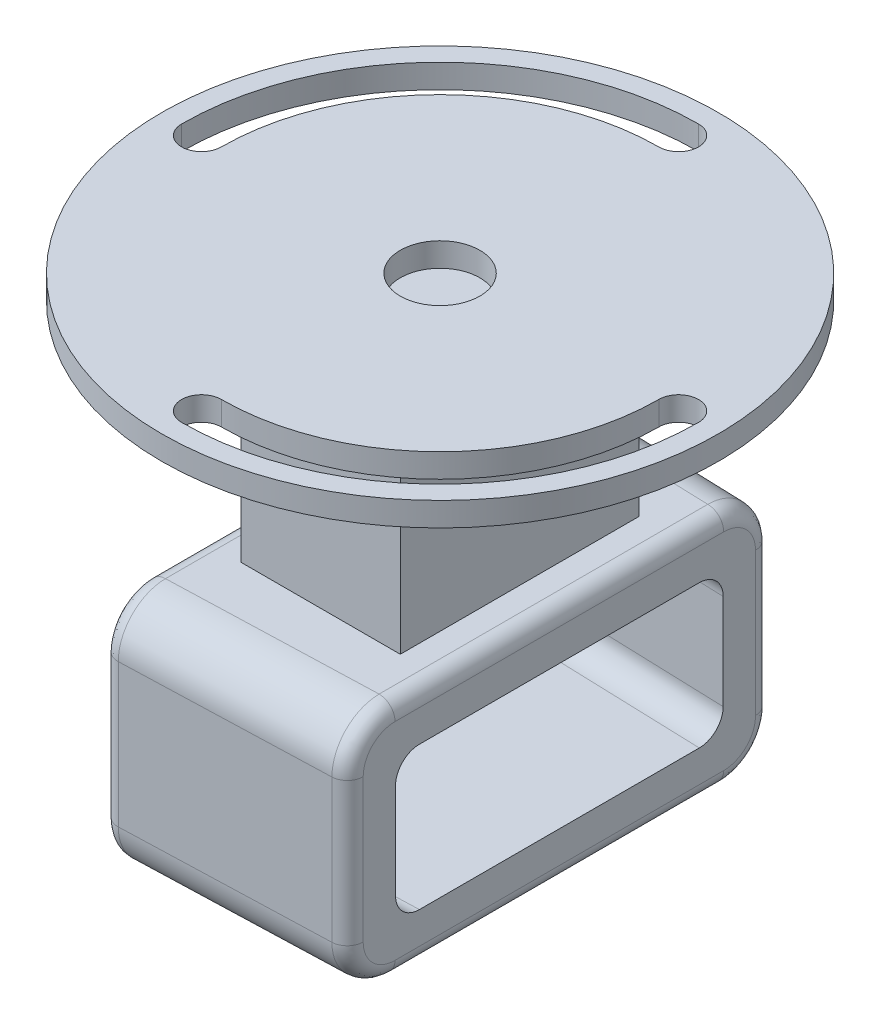
SolidWorks part; units mm, degrees
ref_plane "정면" through (0, 0, 0) normal (0, 0, 1) x (1, 0, 0)
ref_plane "윗면" through (0, 0, 0) normal (0, 1, 0) x (1, 0, 0)
ref_plane "우측면" through (0, 0, 0) normal (1, 0, 0) x (0, 0, -1)
sketch "스케치1" plane through (0, 0, 0) normal (0, 1, 0) x (1, 0, 0)
  circle A0 centre (0, 0) radius 35
  circle A1 centre (0, 0) radius 32.5 construction
  circle A2 centre (0, 0) radius 27.5 construction
  circle A3 centre (0, 0) radius 30 construction
  arc A4 (0, 27.5) -> (0, 32.5) centre (0, 30) ccw
  arc A5 (32.5, 0) -> (27.5, 0) centre (30, 0) ccw
  arc A6 (0, -27.5) -> (0, -32.5) centre (0, -30) ccw
  arc A7 (-32.5, 0) -> (-27.5, 0) centre (-30, 0) ccw
  arc A8 (-27.5, 0) -> (0, 27.5) centre (0, 0) cw
  arc A9 (-32.5, 0) -> (0, 32.5) centre (0, 0) cw
  arc A10 (0, -27.5) -> (27.5, 0) centre (0, 0) ccw
  arc A11 (0, -32.5) -> (32.5, 0) centre (0, 0) ccw
  circle A12 centre (0, 0) radius 5
  dimension "D1" = 70
  dimension "D2" = 65
  dimension "D3" = 60
  dimension "D4" = 55
  dimension "D5" = 10
extrude "보스-돌출1" add sketch "스케치1" along normal blind 3
sketch "스케치2" plane through (0, 0, 0) normal (0, -1, 0) x (1, 0, 0)
  line L1 (-10, -15) -> (10, -15)
  line L2 (-10, -15) -> (-10, 15)
  line L3 (-10, 15) -> (10, 15)
  line L4 (10, -15) -> (10, 15)
  line L5 (-10, -15) -> (10, 15) construction
  line L6 (-10, 15) -> (10, -15) construction
  point P0 (0, 0)
  dimension "D1" = 20
  dimension "D2" = 30
extrude "보스-돌출2" add sketch "스케치2" along normal blind 26
sketch "스케치5" plane through (0, -26, 0) normal (0, -1, 0) x (1, 0, 0)
  line L0 (15, 20.6) -> (15, -20.6)
  line L2 (15, -20.6) -> (-15, -21.6)
  line L3 (-15, -21.6) -> (-15, 21.6)
  line L4 (-15, 21.6) -> (15, 20.6)
  line L5 (15, 0) -> (-15, 0) construction
  line L6 (10, 15) -> (-10, 15) construction
  line L7 (10, -15) -> (10, 15) construction
  line L9 (-10, 15) -> (-10, -15) construction
  point P18 (0, 0)
  dimension "D1" = 41.2
  dimension "D2" = 43.2
  dimension "D3" = 15
  dimension "D4" = 30
  dimension "D5" = 10
extrude "보스-돌출4" add sketch "스케치5" along normal blind 6
sketch "스케치6" plane through (0, -26, 0) normal (0, 1, 0) x (1, 0, 0)
  line L0 (-15, -21.6) -> (-15, -27.6)
  line L1 (-15, -27.6) -> (15, -26.6)
  line L2 (15, -26.6) -> (15, -20.6)
  line L3 (15, -20.6) -> (-15, -21.6)
  line L4 (-15, 21.6) -> (-15, 27.6)
  line L5 (-15, 27.6) -> (15, 26.6)
  line L6 (15, 26.6) -> (15, 20.6)
  line L7 (15, 20.6) -> (-15, 21.6)
  line L8 (-15, 21.6) -> (15, 20.6) construction
  line L9 (15, 20.6) -> (15, -20.6) construction
  dimension "D1" = 6
  dimension "D2" = 6
  dimension "D3" = 6
  dimension "D4" = 6
extrude "보스-돌출5" add sketch "스케치6" against normal blind 30
extrude "보스-돌출6" add sketch "스케치5<2>" against normal blind 6 from surface starting at face at (0, -56, 24.1)
sketch "스케치5<2>" plane through (0, -26, 0) normal (0, -1, 0) x (1, 0, 0) same geometry as "스케치5"
fillet "필렛1" radius 3 4 edges at (0, -32, -21.1) (0, -50, -21.1) (0, -50, 21.1) (0, -32, 21.1)
fillet "필렛2" radius 6 4 edges at (0, -26, 27.1) (0, -26, -27.1) (0, -56, -27.1) (0, -56, 27.1)
fillet "필렛3" radius 2 16 edges at (15, -54.2426, 24.8417) (15, -41, 26.6) (15, -27.7574, 24.8417) (15, -26, 0) (15, -27.7574, -24.8417) (15, -41, -26.6) (15, -54.2426, -24.8417) (-15, -54.2426, -25.8417) (-15, -41, -27.6) (-15, -27.7574, -25.8417) (-15, -26, 0) (-15, -27.7574, 25.8417) (-15, -41, 27.6) (-15, -54.2426, 25.8417) (15, -56, 0) (-15, -56, 0)
ref_plane "평면1" through (0, -56, 0) normal (0, -1, 0) x (-1, 0, 0)
sketch "스케치7" plane through (0, -56, 0) normal (0, -1, 0) x (-1, 0, 0)
  line L0 (0, 0) -> (15, 0) construction
  line L2 (15, 21.6) -> (15, -21.6) construction
  line L3 (15, 9.6) -> (5, 9.6)
  line L4 (5, 9.6) -> (5, 15.6)
  line L5 (5, 15.6) -> (15, 15.6)
  line L6 (15, 15.6) -> (15, 9.6)
  point P5 (15, 0)
  dimension "D1" = 15
  dimension "D2" = 43.2
  dimension "D3" = 6
  dimension "D4" = 12
  dimension "D5" = 10
extrude "컷-돌출1" cut sketch "스케치7" against normal blind 6
fillet "필렛4" radius 1 10 edges at (-14.4142, -55.4142, -9.6) (-14.4142, -55.4142, -15.6) (-10, -50, -15.6) (-10, -50, -9.6) (-15, -52, -15.6) (-15, -52, -9.6) (-9, -56, -9.6) (-9, -56, -15.6) (-5, -56, -12.6) (-5, -50, -12.6)
